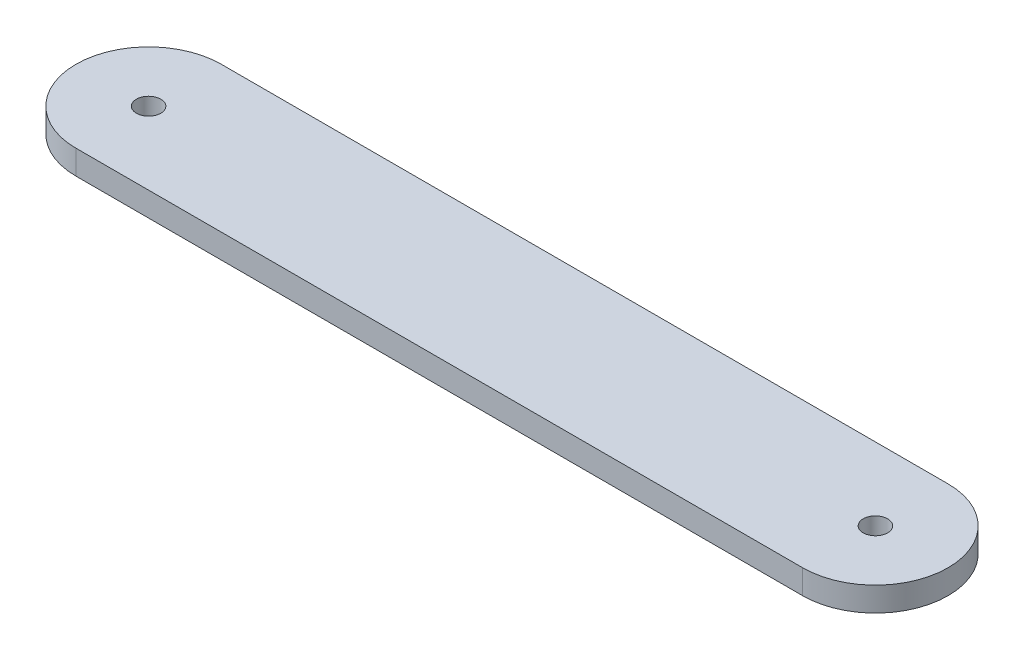
SolidWorks part; units mm, degrees
ref_plane "Front Plane" through (0, 0, 0) normal (0, 0, 1) x (1, 0, 0)
ref_plane "Top Plane" through (0, 0, 0) normal (0, 1, 0) x (1, 0, 0)
ref_plane "Right Plane" through (0, 0, 0) normal (1, 0, 0) x (0, 0, -1)
sketch "Sketch1" plane through (0, 0, 0) normal (0, 1, 0) x (1, 0, 0)
  line L0 (-47.625, 0) -> (47.625, 0) construction
  line L1 (-47.625, 9.525) -> (47.625, 9.525)
  line L2 (-47.625, -9.525) -> (47.625, -9.525)
  arc A0 (-47.625, 9.525) -> (-47.625, -9.525) centre (-47.625, 0) ccw
  arc A1 (47.625, -9.525) -> (47.625, 9.525) centre (47.625, 0) ccw
  point P3 (0, 0)
  dimension "D2" = 9.525
  dimension "D1" = 95.25
extrude "Boss-Extrude1" add sketch "Sketch1" along normal blind 3.175
hole_wizard "M3 Clearance Hole1" positions "Sketch2" profile "Sketch3" hole size "M3" standard "ANSI Metric" end condition through all
sketch "Sketch2" plane through (0, 3.175, 0) normal (0, 1, 0) x (1, 0, 0)
  point P0 (-47.625, 0)
  point P3 (47.625, 0)
sketch "Sketch3" plane through (-47.625, 3.175, 0) normal (1, 0, 0) x (0, 0, 1)
  line L0 (0, 0) -> (0, 3.175)
  line L1 (0, 3.175) -> (1.6, 3.175)
  line L2 (1.6, 3.175) -> (1.6, 0)
  line L5 (1.6, 0) -> (0, 0)
  line L11 (0, -6.35) -> (0, 107.95) construction
  dimension "Thru Hole Dia." = 3.2
  dimension "Thru Hole Depth" = 3.175
